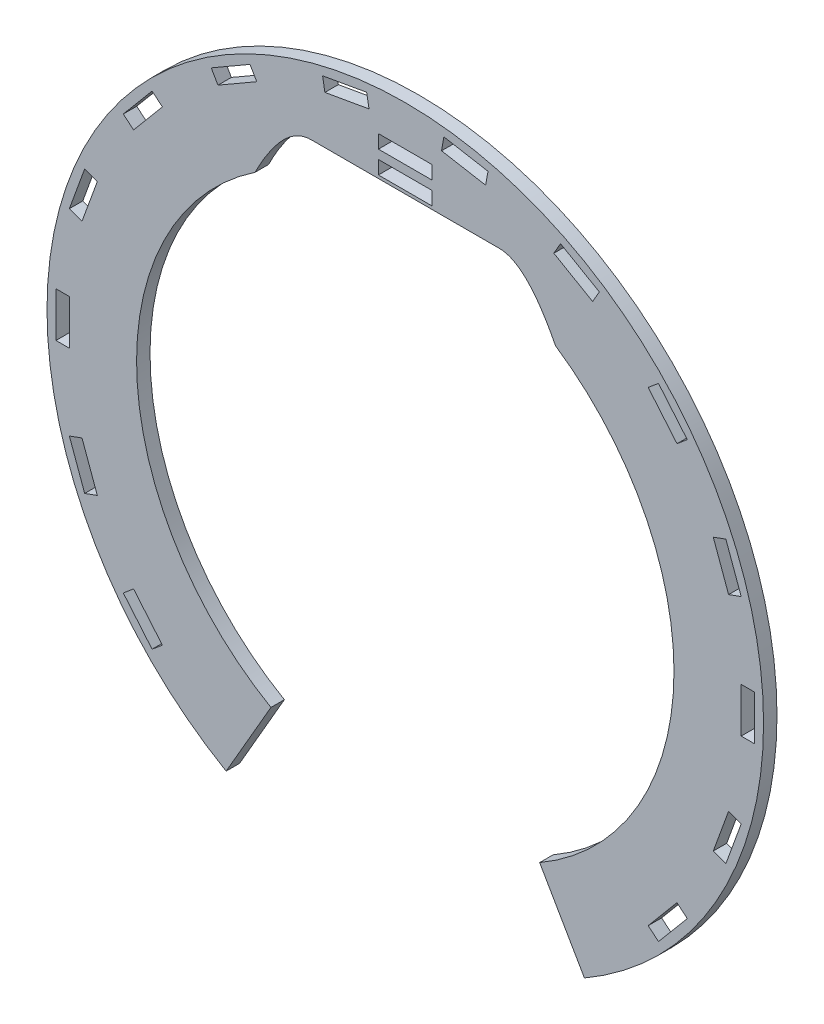
SolidWorks part; units mm, degrees
ref_plane "Přední rovina" through (0, 0, 0) normal (0, 0, 1) x (1, 0, 0)
ref_plane "Horní rovina" through (0, 0, 0) normal (0, 1, 0) x (1, 0, 0)
ref_plane "Pravá rovina" through (0, 0, 0) normal (1, 0, 0) x (0, 0, -1)
sketch "Skica1" plane through (0, 0, 0) normal (0, 0, 1) x (1, 0, 0)
  line L0 (-82.0154, 0) -> (100.8716, 0) construction
  line L1 (0, 71.1227) -> (0, -71.1227) construction
  line L2 (-40, -69.282) -> (-30, -51.9615)
  line L3 (50.2914, 87.1072) -> (-43.916, -76.0647) construction
  line L4 (40, -69.282) -> (-42.9451, 74.3831) construction
  line L5 (40, -69.282) -> (30, -51.9615)
  arc A0 (40, -69.282) -> (-40, -69.282) centre (0, 0) ccw
  arc A1 (30, -51.9615) -> (-30, -51.9615) centre (0, 0) ccw
  dimension "D4" = 80
  dimension "D1" = 30
  dimension "D2" = 30
  dimension "D3" = 20
extrude "Přidat vysunutím1" add sketch "Skica1" along normal blind 3
sketch "Skica3" plane through (0, 0, 3) normal (0, 0, 1) x (1, 0, 0)
  line L0 (-43.3301, 65.05) -> (-34.6699, 70.05)
  line L1 (-67.9025, -69.282) -> (98.6253, -69.282) construction
  line L2 (-40, -69.282) -> (0, 0) construction
  line L3 (0, 0) -> (55.5524, 96.2196) construction
  line L4 (40, -69.282) -> (0, 0) construction
  line L5 (-6, 63) -> (6, 63)
  line L6 (0, 0) -> (96.2196, 55.5524) construction
  line L7 (0, 0) -> (111.1049, 0) construction
  line L8 (0, 0) -> (96.2196, -55.5524) construction
  line L9 (0, 0) -> (55.5524, -96.2196) construction
  line L10 (-6, 63) -> (-6, 66)
  line L11 (0, 0) -> (-55.5524, -96.2196) construction
  line L12 (0, 0) -> (-96.2196, -55.5524) construction
  line L13 (0, 0) -> (-111.1049, 0) construction
  line L14 (0, 0) -> (-96.2196, 55.5524) construction
  line L15 (0, 0) -> (-55.5524, 96.2196) construction
  line L16 (0, 0) -> (0, 111.1049) construction
  line L17 (0, 0) -> (0, -111.1049) construction
  line L18 (-6, 66) -> (6, 66)
  line L19 (6, 63) -> (6, 66)
  line L20 (-6, 63) -> (6, 66) construction
  line L21 (-6, 66) -> (6, 63) construction
  line L22 (-43.3301, 65.05) -> (-41.8301, 62.4519)
  line L23 (-34.6699, 70.05) -> (-33.1699, 67.4519)
  line L24 (-41.8301, 62.4519) -> (-33.1699, 67.4519)
  line L25 (-43.3301, 65.05) -> (-33.1699, 67.4519) construction
  line L26 (-34.6699, 70.05) -> (-41.8301, 62.4519) construction
  line L27 (-18.4686, 75.9468) -> (-8.6205, 77.6832)
  line L28 (-18.4686, 75.9468) -> (-17.9477, 72.9923)
  line L29 (-17.9477, 72.9923) -> (-8.0996, 74.7288)
  line L30 (-8.6205, 77.6832) -> (-8.0996, 74.7288)
  line L31 (8.6205, 77.6832) -> (18.4686, 75.9468)
  line L32 (8.6205, 77.6832) -> (8.0996, 74.7288)
  line L33 (8.0996, 74.7288) -> (17.9477, 72.9923)
  line L34 (18.4686, 75.9468) -> (17.9477, 72.9923)
  line L35 (34.6699, 70.05) -> (43.3301, 65.05)
  line L36 (34.6699, 70.05) -> (33.1699, 67.4519)
  line L37 (33.1699, 67.4519) -> (41.8301, 62.4519)
  line L38 (43.3301, 65.05) -> (41.8301, 62.4519)
  line L39 (56.5375, 53.9677) -> (62.9654, 46.3072)
  line L40 (56.5375, 53.9677) -> (54.2394, 52.0393)
  line L41 (54.2394, 52.0393) -> (60.6673, 44.3788)
  line L42 (62.9654, 46.3072) -> (60.6673, 44.3788)
  line L43 (71.5859, 31.376) -> (75.0061, 21.9791)
  line L44 (71.5859, 31.376) -> (68.7668, 30.35)
  line L45 (68.7668, 30.35) -> (72.187, 20.953)
  line L46 (75.0061, 21.9791) -> (72.187, 20.953)
  line L47 (78, 5) -> (78, -5)
  line L48 (78, 5) -> (75, 5)
  line L49 (75, 5) -> (75, -5)
  line L50 (78, -5) -> (75, -5)
  line L51 (75.0061, -21.9791) -> (71.5859, -31.376)
  line L52 (75.0061, -21.9791) -> (72.187, -20.953)
  line L53 (72.187, -20.953) -> (68.7668, -30.35)
  line L54 (71.5859, -31.376) -> (68.7668, -30.35)
  line L55 (62.9654, -46.3072) -> (56.5375, -53.9677)
  line L56 (62.9654, -46.3072) -> (60.6673, -44.3788)
  line L57 (60.6673, -44.3788) -> (54.2394, -52.0393)
  line L58 (56.5375, -53.9677) -> (54.2394, -52.0393)
  line L59 (43.3301, -65.05) -> (34.6699, -70.05) [skipped]
  line L60 (43.3301, -65.05) -> (41.8301, -62.4519) [skipped]
  line L61 (41.8301, -62.4519) -> (33.1699, -67.4519) [skipped]
  line L62 (34.6699, -70.05) -> (33.1699, -67.4519) [skipped]
  line L63 (18.4686, -75.9468) -> (8.6205, -77.6832) [skipped]
  line L64 (18.4686, -75.9468) -> (17.9477, -72.9923) [skipped]
  line L65 (17.9477, -72.9923) -> (8.0996, -74.7288) [skipped]
  line L66 (8.6205, -77.6832) -> (8.0996, -74.7288) [skipped]
  line L67 (-8.6205, -77.6832) -> (-18.4686, -75.9468) [skipped]
  line L68 (-8.6205, -77.6832) -> (-8.0996, -74.7288) [skipped]
  line L69 (-8.0996, -74.7288) -> (-17.9477, -72.9923) [skipped]
  line L70 (-18.4686, -75.9468) -> (-17.9477, -72.9923) [skipped]
  line L71 (-34.6699, -70.05) -> (-43.3301, -65.05) [skipped]
  line L72 (-34.6699, -70.05) -> (-33.1699, -67.4519) [skipped]
  line L73 (-33.1699, -67.4519) -> (-41.8301, -62.4519) [skipped]
  line L74 (-43.3301, -65.05) -> (-41.8301, -62.4519) [skipped]
  line L75 (-56.5375, -53.9677) -> (-62.9654, -46.3072)
  line L76 (-56.5375, -53.9677) -> (-54.2394, -52.0393)
  line L77 (-54.2394, -52.0393) -> (-60.6673, -44.3788)
  line L78 (-62.9654, -46.3072) -> (-60.6673, -44.3788)
  line L79 (-71.5859, -31.376) -> (-75.0061, -21.9791)
  line L80 (-71.5859, -31.376) -> (-68.7668, -30.35)
  line L81 (-68.7668, -30.35) -> (-72.187, -20.953)
  line L82 (-75.0061, -21.9791) -> (-72.187, -20.953)
  line L83 (-78, -5) -> (-78, 5)
  line L84 (-78, -5) -> (-75, -5)
  line L85 (-75, -5) -> (-75, 5)
  line L86 (-78, 5) -> (-75, 5)
  line L87 (-75.0061, 21.9791) -> (-71.5859, 31.376)
  line L88 (-75.0061, 21.9791) -> (-72.187, 20.953)
  line L89 (-72.187, 20.953) -> (-68.7668, 30.35)
  line L90 (-71.5859, 31.376) -> (-68.7668, 30.35)
  line L91 (-62.9654, 46.3072) -> (-56.5375, 53.9677)
  line L92 (-62.9654, 46.3072) -> (-60.6673, 44.3788)
  line L93 (-60.6673, 44.3788) -> (-54.2394, 52.0393)
  line L94 (-56.5375, 53.9677) -> (-54.2394, 52.0393)
  line L96 (6, 68) -> (-6, 68)
  line L97 (6, 68) -> (6, 71)
  line L98 (6, 71) -> (-6, 71)
  line L99 (-6, 68) -> (-6, 71)
  line L100 (6, 68) -> (-6, 71) construction
  line L101 (6, 71) -> (-6, 68) construction
  arc A0 (30, -51.9615) -> (-30, -51.9615) centre (0, 0) ccw construction
  point P0 (0, 63)
  point P3 (0, 0)
  point P4 (-40, -69.282)
  point P5 (40, -69.282)
  point P30 (0, 0)
  point P33 (0, 60)
  point P34 (0, 69.5)
  point P35 (-38.25, 66.2509)
  point P37 (-30, 51.9615)
  point P39 (-38.3657, 66.4513)
  point P112 (0, 0)
  dimension "D2" = 3
  dimension "D3" = 12
  dimension "D4" = 3
  dimension "D5" = 5
  dimension "D6" = 10
  dimension "D7" = 3
  dimension "D9" = 78
  dimension "D10" = 12
  dimension "D11" = 3
  dimension "D12" = 2
  dimension "D1" = 12
  dimension "D8" = 18
extrude "Odebrat vysunutím1" cut sketch "Skica3" against normal blind 3
sketch "Skica4" plane through (0, 0, 0) normal (0, 0, -1) x (-1, 0, 0)
  line L0 (0, 85.4839) -> (0, 30.8548) construction
  line L1 (-33.5345, 49.7538) -> (33.5345, 49.7538) construction
  line L2 (-21, 62.31) -> (21, 62.31)
  line L6 (-21, 83.0379) -> (-21, 33.4147) construction
  line L7 (21, 83.0379) -> (21, 33.4147) construction
  line L8 (-37.7575, 62.31) -> (42.834, 62.31) construction
  line L9 (-21, 49.7538) -> (-34.141, 62.8947) construction
  line L10 (-21, 62.31) -> (-27.1966, 62.31) construction
  line L11 (21, 49.7538) -> (35.1421, 63.8959) construction
  line L12 (-33.5345, 47.1737) -> (-33.5345, 65.3835) construction
  line L13 (-27.1966, 62.31) -> (-33.5345, 49.7538) construction
  line L14 (21, 62.31) -> (27.1966, 62.31) construction
  line L15 (27.1966, 62.31) -> (33.5345, 49.7538) construction
  line L16 (-33.5345, 49.7538) -> (33.5345, 49.7538)
  arc A0 (30, -51.9615) -> (-30, -51.9615) centre (0, 0) ccw construction
  spline S0 degree 2 poles (-21, 62.31) (-27.1966, 62.31) (-33.5345, 49.7538) knots 0 0 0 1 1 1
  spline S1 degree 2 poles (21, 62.31) (27.1966, 62.31) (33.5345, 49.7538) knots 0 0 0 1 1 1
  point P2 (0, 57.56)
  point P26 (0, 0)
  point P27 (0, 0)
  point P29 (0, 0)
  dimension "D1" = 45
  dimension "D2" = 45
extrude "Odebrat vysunutím3" cut sketch "Skica4" against normal blind 3 contours L2 S1 L16 S0
